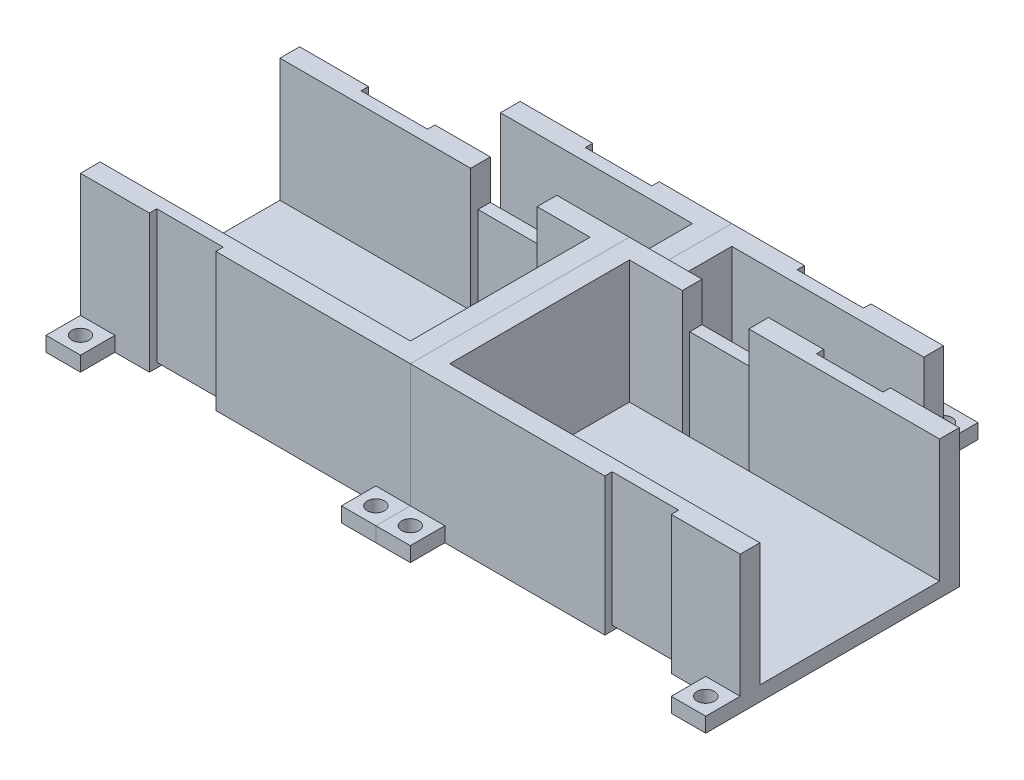
SolidWorks part; units mm, degrees
ref_plane "Front Plane" through (0, 0, 0) normal (0, 0, 1) x (1, 0, 0)
ref_plane "Top Plane" through (0, 0, 0) normal (0, 1, 0) x (1, 0, 0)
ref_plane "Right Plane" through (0, 0, 0) normal (1, 0, 0) x (0, 0, -1)
sketch "Sketch1" plane through (0, 0, 0) normal (0, 1, 0) x (1, 0, 0)
  line L0 (-33.5, 7.85) -> (29.5, 7.85)
  line L1 (-33.5, -32.65) -> (33.5, -32.65)
  line L2 (-33.5, -32.65) -> (-33.5, 11.85)
  line L4 (33.5, -32.65) -> (33.5, 32.65)
  line L5 (-33.5, 11.85) -> (29.5, 11.85)
  line L6 (29.5, 11.85) -> (29.5, 28.65)
  line L7 (29.5, 7.85) -> (29.5, -28.65)
  line L8 (29.5, -28.65) -> (-33.5, -28.65)
  line L9 (29.5, 28.65) -> (-9.5, 28.65)
  line L10 (-19.5, -31.15) -> (-6, -31.15)
  line L11 (-19.5, -31.15) -> (-19.5, -32.65)
  line L12 (-19.5, -32.65) -> (-6, -32.65)
  line L13 (-6, -31.15) -> (-6, -32.65)
  line L14 (-19.5, -31.15) -> (-6, -32.65) construction
  line L15 (-19.5, -32.65) -> (-6, -31.15) construction
  line L16 (-19.5, 10.35) -> (-6, 10.35)
  line L17 (-19.5, 10.35) -> (-19.5, 11.85)
  line L18 (-19.5, 11.85) -> (-6, 11.85)
  line L19 (-6, 10.35) -> (-6, 11.85)
  line L20 (-19.5, 10.35) -> (-6, 11.85) construction
  line L21 (-19.5, 11.85) -> (-6, 10.35) construction
  line L22 (-9.5, 28.65) -> (-9.5, 32.65)
  line L23 (-9.5, 32.65) -> (33.5, 32.65)
  line L24 (-9.5, 28.65) -> (-9.5, 11.85)
  line L25 (5.25, 31.15) -> (18.75, 31.15)
  line L26 (5.25, 31.15) -> (5.25, 32.65)
  line L27 (5.25, 32.65) -> (18.75, 32.65)
  line L28 (18.75, 31.15) -> (18.75, 32.65)
  line L29 (5.25, 31.15) -> (18.75, 32.65) construction
  line L30 (5.25, 32.65) -> (18.75, 31.15) construction
  line L31 (5.25, 9.35) -> (18.75, 9.35)
  line L32 (5.25, 9.35) -> (5.25, 7.85)
  line L33 (5.25, 7.85) -> (18.75, 7.85)
  line L34 (18.75, 9.35) -> (18.75, 7.85)
  line L35 (5.25, 9.35) -> (18.75, 7.85) construction
  line L36 (5.25, 7.85) -> (18.75, 9.35) construction
  line L37 (5.25, 31.15) -> (5.25, 9.35)
  line L38 (18.75, 9.35) -> (18.75, 31.15)
  line L39 (-19.5, 10.35) -> (-19.5, -31.15)
  line L40 (-6, -31.15) -> (-6, 10.35)
  line L41 (29.5, 11.85) -> (33.5, 11.85)
  line L42 (-26.5, -39.65) -> (-33.5, -39.65)
  line L43 (-26.5, -39.65) -> (-26.5, -32.65)
  line L44 (-26.5, -32.65) -> (-33.5, -32.65)
  line L45 (-33.5, -39.65) -> (-33.5, -32.65)
  line L46 (-26.5, -39.65) -> (-33.5, -32.65) construction
  line L47 (-26.5, -32.65) -> (-33.5, -39.65) construction
  line L48 (26.5, -39.65) -> (33.5, -39.65)
  line L49 (26.5, -39.65) -> (26.5, -32.65)
  line L50 (26.5, -32.65) -> (33.5, -32.65)
  line L51 (33.5, -39.65) -> (33.5, -32.65)
  line L52 (26.5, -39.65) -> (33.5, -32.65) construction
  line L53 (26.5, -32.65) -> (33.5, -39.65) construction
  line L54 (-2.5, 39.65) -> (-9.5, 39.65)
  line L55 (-2.5, 39.65) -> (-2.5, 32.65)
  line L56 (-2.5, 32.65) -> (-9.5, 32.65)
  line L57 (-9.5, 39.65) -> (-9.5, 32.65)
  line L58 (-2.5, 39.65) -> (-9.5, 32.65) construction
  line L59 (-2.5, 32.65) -> (-9.5, 39.65) construction
  circle A0 centre (-30, -36.15) radius 1.75
  circle A1 centre (30, -36.15) radius 1.75
  circle A2 centre (-6, 36.15) radius 1.75
  point P0 (12, 31.9)
  point P8 (-12.75, -31.9)
  point P15 (-12.75, 11.1)
  point P27 (12, 8.6)
  point P32 (-30, -36.15)
  point P34 (30, -36.15)
  point P37 (0, -32.65)
  point P39 (33.5, 0)
  point P41 (12, 32.65)
  point P42 (-6, 36.15)
  dimension "D12" = 3.5
  dimension "D1" = 36.5
  dimension "D2" = 63
  dimension "D3" = 4
  dimension "D4" = 4
  dimension "D5" = 4
  dimension "D6" = 4
  dimension "D7" = 13.5
  dimension "D8" = 1.5
  dimension "D9" = 14
  dimension "D10" = 16.8
  dimension "D11" = 39
  dimension "D13" = 7
extrude "Boss-Extrude1" add sketch "Sketch1" along normal blind 3 contours L40 L8 L7 L0 | L8 L40 L0 L39 | L39 L0 L2 L8 | L39 L8 L2 L1 L11 | L10 L40 L8 L39 | L13 L10 L11 L1 | L40 L13 L1 L4 L23 L28 L38 L9 L6 L5 L34 L0 L7 L8 | L37 L26 L23 L22 L9 | L25 L28 L23 L26 | L9 L38 L25 L37 | L5 L38 L9 L37 | L37 L9 L24 L18 L5 | L38 L5 L6 L9 | L39 L17 L5 L2 L0 | L16 L19 L18 L5 L17 | L0 L40 L16 L39 | L40 L0 L32 L37 L5 L19 | L31 L38 L5 L37 | L34 L31 L32 L0 | L54 L57 L23 L55 A2 | L45 L42 L43 L1 A0 | L48 L51 L1 L49 A1 | L6 L41 L4 L23 L28 L38 L9 region at (12, 0, -8.6) region at (11.75, 0, 10.4) region at (-0.375, 0, -9.85) region at (19.345, 0, -8.6) region at (-12.75, 0, 10.4) region at (-12.75, 0, -9.1) region at (12, 0, -10.6) region at (-26.5, 0, 10.4) region at (-26.5, 0, -9.85) region at (-12.75, 0, 29.9) region at (-12.75, 0, -11.1) region at (12, 0, -20.25) region at (-2.125, 0, -20.25) region at (24.125, 0, -20.25) region at (-26.5, 0, 30.65) region at (-12.75, 0, 31.9) region at (12, 0, -29.9) region at (-2.125, 0, -30.65) region at (29.755, 0, -20.25) region at (12, 0, -31.9) region at (-30, 0, 32.749) region at (30, 0, 32.749) region at (-9.401, 0, -36.15)
extrude "Boss-Extrude2" add sketch "Sketch1<5>" along normal blind 25 from surface contours L39 L8 L2 L1 L11 | L10 L40 L8 L39 | L41 L5 L38 L34 L0 L7 L8 L40 L13 L1 L4 | L40 L0 L32 L37 L5 L19 | L0 L40 L16 L39 | L39 L17 L5 L2 L0 region at (-0.375, 0, -9.85) region at (19.345, 0, -8.6) region at (-12.75, 0, -9.1) region at (-26.5, 0, -9.85) region at (-12.75, 0, 29.9) region at (-26.5, 0, 30.65) starting at face at (-2, 3, 4.6333)
sketch "Sketch1<5>" plane through (0, 0, 0) normal (0, 1, 0) x (1, 0, 0) same geometry as "Sketch1"
extrude "Boss-Extrude3" add sketch "Sketch1<6>" along normal blind 20 contours L6 L41 L4 L23 L28 L38 L9 | L37 L26 L23 L22 L9 | L9 L38 L25 L37 | L31 L38 L5 L37 region at (12, 0, -10.6) region at (12, 0, -29.9) region at (-2.125, 0, -30.65) region at (29.755, 0, -20.25)
sketch "Sketch1<6>" plane through (0, 0, 0) normal (0, 1, 0) x (1, 0, 0) same geometry as "Sketch1"
extrude "Cut-Extrude1" cut sketch "Sketch1<7>" against normal through all both and the other way through all contours L25 L28 L23 L26 | L34 L31 L32 L0 | L16 L19 L18 L5 L17 | L13 L10 L11 L1 region at (12, 0, -8.6) region at (-12.75, 0, -11.1) region at (-12.75, 0, 31.9) region at (12, 0, -31.9)
sketch "Sketch1<7>" plane through (0, 0, 0) normal (0, 1, 0) x (1, 0, 0) same geometry as "Sketch1"
extrude "Cut-Extrude2" cut sketch "Sketch1<8>" along normal blind 1 contours L5 L38 L9 L37 | L9 L38 L25 L37 | L31 L38 L5 L37 | L8 L40 L0 L39 | L0 L40 L16 L39 | L10 L40 L8 L39 region at (-12.75, 0, 10.4) region at (-12.75, 0, -9.1) region at (12, 0, -10.6) region at (-12.75, 0, 29.9) region at (12, 0, -20.25) region at (12, 0, -29.9)
sketch "Sketch1<8>" plane through (0, 0, 0) normal (0, 1, 0) x (1, 0, 0) same geometry as "Sketch1"
mirror "Mirror1" about plane through (33.5, 3, 0) normal (-1, 0, 0) of bodies 109
